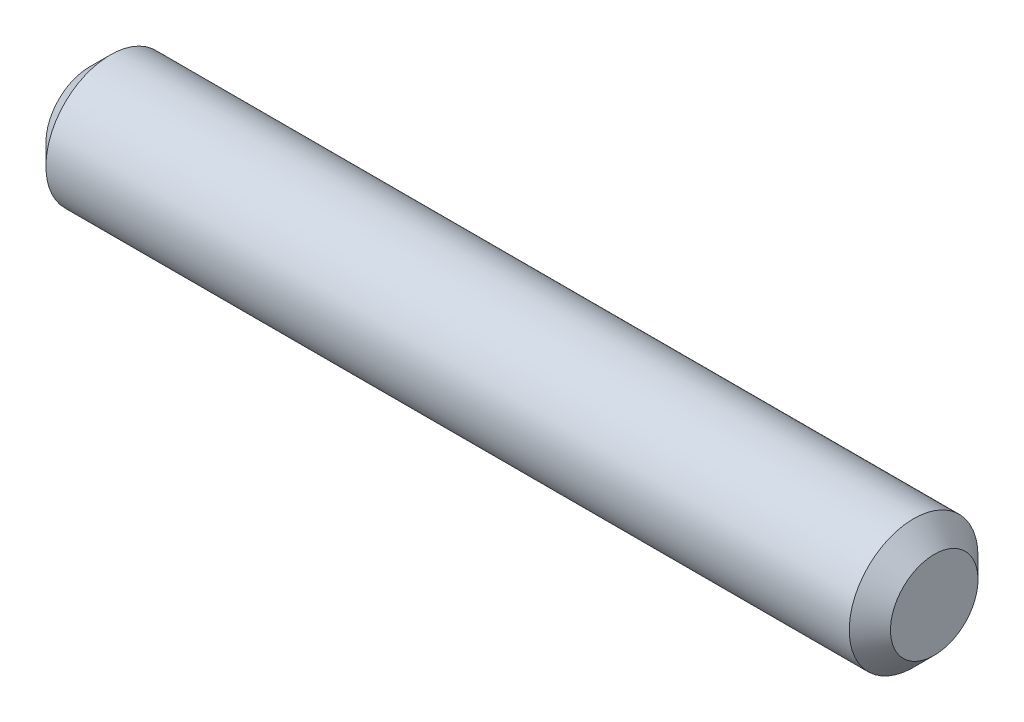
SolidWorks part; units mm, degrees
material "6061-T6 (SS)"
ref_plane "Front" through (0, 0, 0) normal (0, 0, 1) x (1, 0, 0)
ref_plane "Top" through (0, 0, 0) normal (0, 1, 0) x (1, 0, 0)
ref_plane "Right" through (0, 0, 0) normal (1, 0, 0) x (0, 0, -1)
ref_axis "side-side" through (80.9, 0, 0) along (-1, 0, 0)
ref_axis "up-down" through (0, 50, 0) along (0, -1, 0)
ref_axis "front-back" through (0, 0, -80.9) along (0, 0, 1)
sketch "Sketch1" plane through (0, 0, 0) normal (1, 0, 0) x (0, 0, -1)
  circle A0 centre (0, 0) radius 1.5875
  dimension "D1" = 3.175
extrude "Boss-Extrude1" add sketch "Sketch1" along normal mid plane 20.828
chamfer "Chamfer1" distance 0.508 angle 45 2 edges at (-10.414, 0, -1.5875) (10.414, 0, -1.5875)
